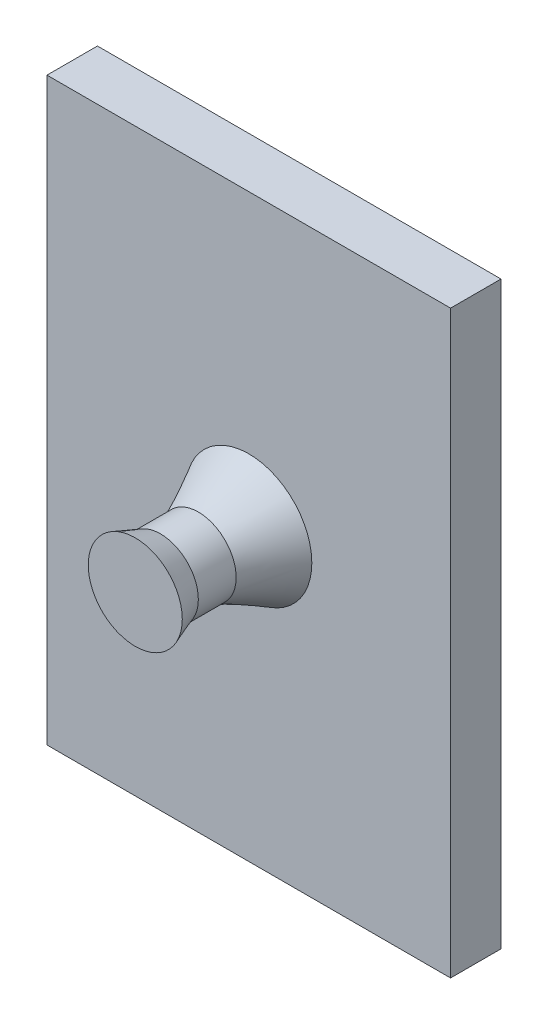
SolidWorks part; units mm, degrees
ref_plane "Front Plane" through (0, 0, 0) normal (0, 0, 1) x (1, 0, 0)
ref_plane "Top Plane" through (0, 0, 0) normal (0, 1, 0) x (1, 0, 0)
ref_plane "Right Plane" through (0, 0, 0) normal (1, 0, 0) x (0, 0, -1)
sketch "Sketch1" plane through (0, 0, 0) normal (0, 0, 1) x (1, 0, 0)
  line L1 (0, 0) -> (16, 0)
  line L2 (0, 0) -> (0, 23)
  line L3 (0, 23) -> (16, 23)
  line L4 (16, 0) -> (16, 23)
  dimension "D1" = 16
  dimension "D2" = 23
extrude "Boss-Extrude1" add sketch "Sketch1" along normal blind 2
sketch "Sketch2" plane through (0, 0, 2) normal (0, 0, 1) x (1, 0, 0)
  line L0 (16, 0) -> (16, 23) construction
  line L1 (0, 0) -> (16, 0) construction
  circle A0 centre (8, 11.5) radius 2.5
  point P5 (16, 11.5)
  point P9 (8, 0)
  dimension "D1" = 5
ref_plane "Plane1" through (0, 0, 4) normal (0, 0, 1) x (1, 0, 0)
sketch "Sketch4" plane through (0, 0, 4) normal (0, 0, 1) x (1, 0, 0)
  circle A0 centre (8, 11.5) radius 1.5
  dimension "D1" = 3
loft "Loft1" add profiles "Sketch2", "Sketch4" connector at (10.5, 11.5, 2) connector at (9.3822, 10.9173, 4)
sketch "Sketch6" plane through (0, 0, 4) normal (0, 0, 1) x (1, 0, 0)
  circle A0 centre (8, 11.5) radius 1.5 construction
  circle A1 centre (8, 11.5) radius 1.5
extrude "Boss-Extrude3" add sketch "Sketch6" along normal blind 1.5
sketch "Sketch7" plane through (0, 0, 5.5) normal (0, 0, 1) x (1, 0, 0)
  circle A1 centre (8, 11.5) radius 1.5
  circle A2 centre (8, 11.5) radius 1.5
  dimension "D1" = 0
extrude "Boss-Extrude4" add sketch "Sketch7" along normal blind 1 draft 20 draft outward yes
